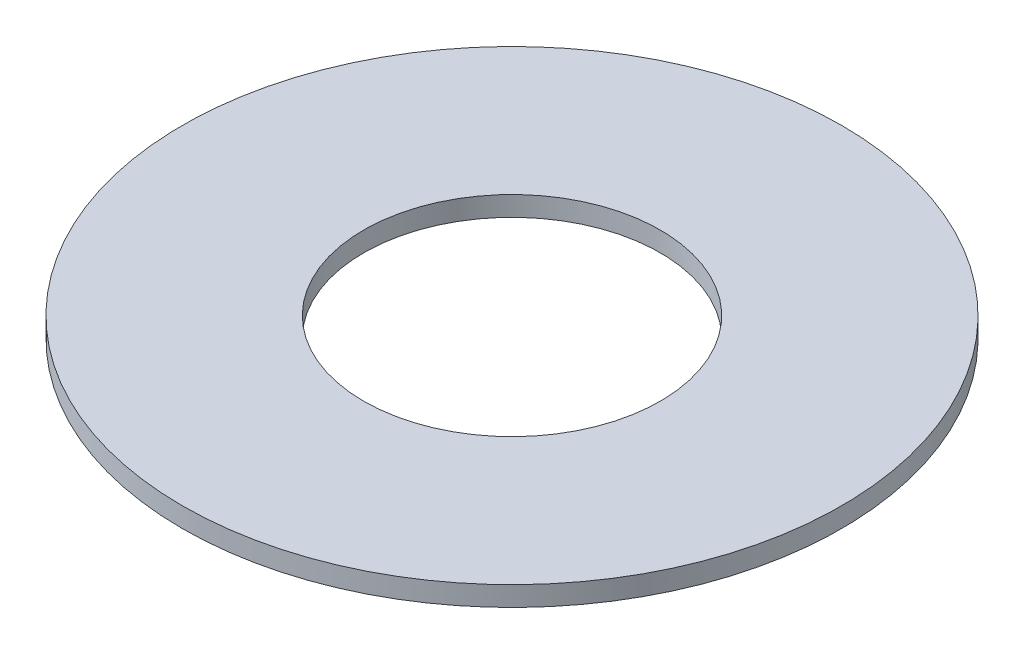
SolidWorks part; units mm, degrees
ref_plane "Front Plane" through (0, 0, 0) normal (0, 0, 1) x (1, 0, 0)
ref_plane "Top Plane" through (0, 0, 0) normal (0, 1, 0) x (1, 0, 0)
ref_plane "Right Plane" through (0, 0, 0) normal (1, 0, 0) x (0, 0, -1)
sketch "Sketch1" plane through (0, 0, 0) normal (0, 1, 0) x (1, 0, 0)
  circle A0 centre (0, 0) radius 100
  dimension "FLANGE_OD" = 200
extrude "Boss-Extrude1" add sketch "Sketch1" along normal blind 6
sketch "Sketch2" plane through (0, 0, 0) normal (0, 1, 0) x (1, 0, 0)
  circle A0 centre (0, 0) radius 45
  dimension "BORE_D" = 90
extrude "Cut-Extrude1" cut sketch "Sketch2" along normal through all
sketch "Sketch3" plane through (0, 6, 0) normal (0, 1, 0) x (1, 0, 0)
  circle A0 centre (0, 0) radius 32.7994 construction
  circle A1 centre (-32.7994, 0) radius 1.863
  dimension "BOLT_D" = 3.7261
  dimension "BOLT_PCD" = 65.5987
extrude "Cut-Extrude2" cut sketch "Sketch3" against normal blind 3.9046 rebuild error yes
pattern_circular "CirPattern1" count 6 over 360 rebuild error yes
